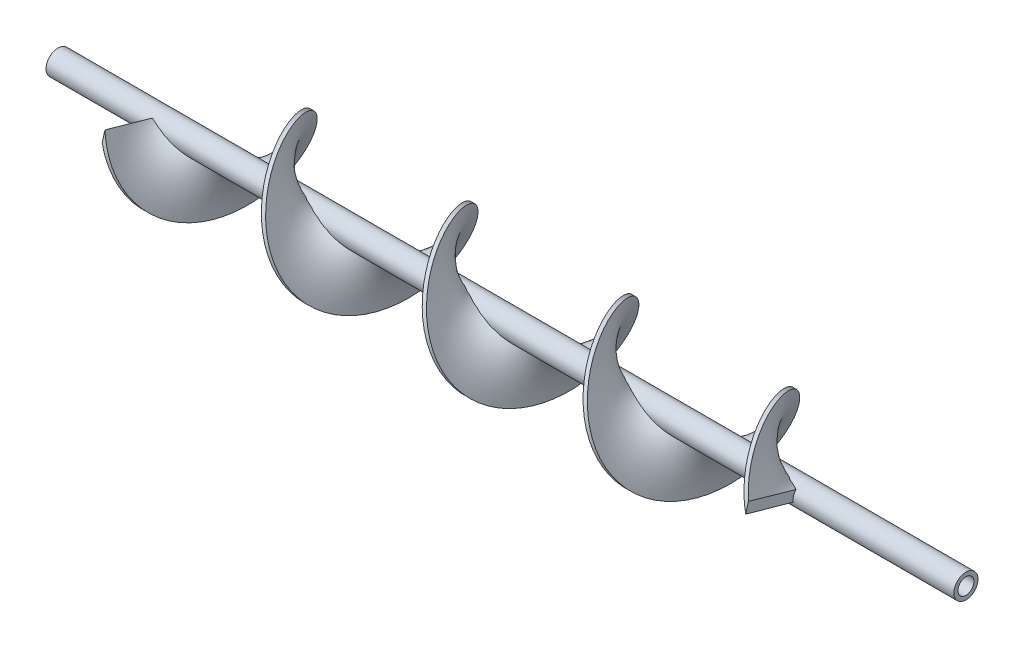
SolidWorks part; units mm, degrees
material "Brass"
ref_plane "Vorderansicht" through (0, 0, 0) normal (0, 0, 1) x (1, 0, 0)
ref_plane "Draufsicht" through (0, 0, 0) normal (0, 1, 0) x (1, 0, 0)
ref_plane "Seitenansicht" through (0, 0, 0) normal (1, 0, 0) x (0, 0, -1)
sketch "Skizze3" plane through (0, 0, 0) normal (1, 0, 0) x (0, 0, -1)
  circle A0 centre (0, 0) radius 6
  circle A1 centre (0, 0) radius 4
  dimension "D1" = 12
  dimension "D2" = 2
extrude "Aufsatz-Linear austragen1" add sketch "Skizze3" against normal blind 415 and the other way blind 51.5 separate body
ref_plane "Ref_of_Spiral" through (36.5, 0, 0) normal (1, 0, 0) x (0, 0, -1)
sketch "Skizze1" plane through (36.5, 0, 0) normal (1, 0, 0) x (0, 0, -1)
  circle A0 centre (0, 0) radius 4
  dimension "D1" = 8
curve "Spirale/Helix1" pitch 80 height 320 radius 4 centre (36.5, 0, 0) axis (-1, 0, 0) start towards (0, 0, -1)
sketch "Skizze2" plane through (0, 0, 0) normal (1, 0, 0) x (0, 0, -1)
  line L0 (19.3938, 0) -> (56.2084, 0) construction
  line L2 (3.1225, -2.5) -> (30, -2.5)
  line L4 (3.1225, 2.5) -> (30, 2.5)
  line L5 (30, -2.5) -> (30, 2.5)
  arc A1 (3.1225, -2.5) -> (3.1225, 2.5) centre (0, 0) ccw
  dimension "D1" = 30
  dimension "D3" = 5
sweep "Austragung1" add profiles "Skizze2" path "Spirale/Helix1"
sketch "Sketch1" plane through (51.5, 0, 0) normal (1, 0, 0) x (0, 0, -1)
  circle A0 centre (0, 0) radius 4
  circle A1 centre (0, 0) radius 6
extrude "Boss-Extrude1" add sketch "Sketch1" along normal blind 65
sketch "Sketch2" plane through (-415, 0, 0) normal (-1, 0, 0) x (0, 0, 1)
  circle A0 centre (0, 0) radius 6
extrude "Cut-Extrude1" cut sketch "Sketch2" against normal blind 80
